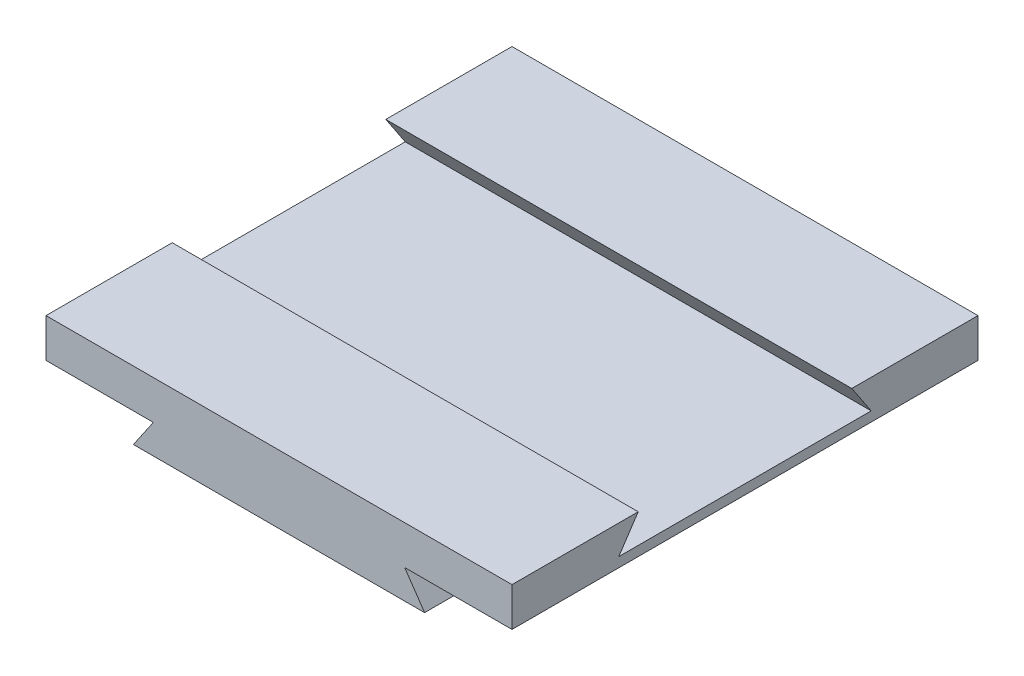
SolidWorks part; units mm, degrees
ref_plane "Спереди" through (0, 0, 0) normal (0, 0, 1) x (1, 0, 0)
ref_plane "Сверху" through (0, 0, 0) normal (0, 1, 0) x (1, 0, 0)
ref_plane "Справа" through (0, 0, 0) normal (1, 0, 0) x (0, 0, -1)
sketch "Эскиз1" plane through (0, 0, 0) normal (0, 0, 1) x (1, 0, 0)
  line L0 (0, 0) -> (75, 0)
  line L1 (75, 0) -> (64.72, 15)
  line L2 (64.72, 15) -> (120, 15)
  line L3 (120, 15) -> (120, 35)
  line L4 (120, 35) -> (0, 35)
  line L5 (0, 56.4782) -> (0, 0) construction
  line L6 (-120, 35) -> (0, 35)
  line L7 (-120, 15) -> (-120, 35)
  line L8 (-64.72, 15) -> (-120, 15)
  line L9 (-75, 0) -> (-64.72, 15)
  line L10 (0, 0) -> (-75, 0)
  line L11 (-75, 0) -> (75, 0) construction
  point P3 (0, 0)
  point P8 (0.9855, 51.4782)
  point P9 (-1.8154, -27.6193)
  point P12 (0, -26.3226)
  point P14 (0, 0)
  point P18 (0, 0)
  point P19 (0, 0)
  point P20 (0, 25.0467)
  point P21 (0, 0)
  point P22 (0, 0)
  point P23 (-96.7885, 0)
  point P26 (51.0892, 0)
  point P27 (51.0892, 0)
  point P28 (0, 0)
  point P29 (0, -1.6826)
  dimension "D1" = 20
  dimension "D2" = 75
  dimension "D3" = 120
extrude "Бобышка-Вытянуть1" add sketch "Эскиз1" along normal blind 240
sketch "Эскиз2" plane through (-120, 0, 0) normal (-1, 0, 0) x (0, 0, 1)
  line L0 (120, 35) -> (120, -3.231) construction
  line L1 (240, 35) -> (0, 35) construction
  line L6 (65, 35) -> (175, 35)
  line L7 (175, 35) -> (185, 20)
  line L8 (185, 20) -> (55, 20)
  line L9 (65, 35) -> (55, 20)
  point P4 (0, 0)
  point P9 (120, 20)
  dimension "D1" = 65
  dimension "D2" = 15
  dimension "D3" = 55
extrude "Вырез-Вытянуть1" cut sketch "Эскиз2" against normal through all
